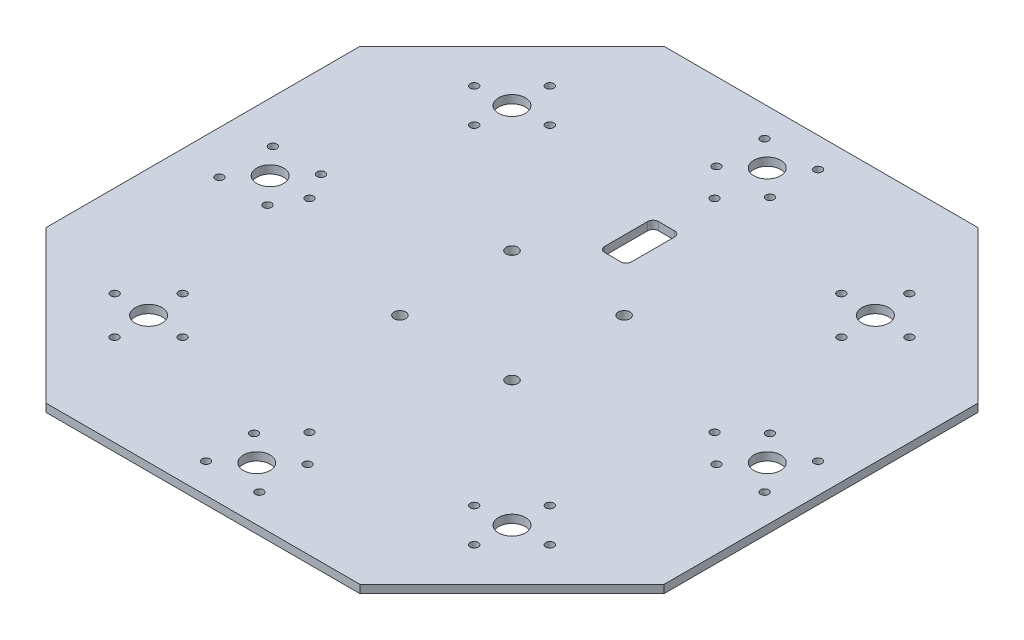
SolidWorks part; units mm, degrees
ref_plane "Front Plane" through (0, 0, 0) normal (0, 0, 1) x (1, 0, 0)
ref_plane "Top Plane" through (0, 0, 0) normal (0, 1, 0) x (1, 0, 0)
ref_plane "Right Plane" through (0, 0, 0) normal (1, 0, 0) x (0, 0, -1)
sketch "Sketch1" plane through (0, 0, 0) normal (0, 1, 0) x (1, 0, 0)
  line L1 (0, 0) -> (230, 0)
  line L2 (0, 0) -> (0, 230)
  line L3 (0, 230) -> (230, 230)
  line L4 (230, 0) -> (230, 230)
  dimension "D1" = 230
  dimension "D2" = 230
extrude "Boss-Extrude1" add sketch "Sketch1" along normal blind 3
fillet "Chamfer2" radius 56.5685 1 edges at (0, 1.5, 0) type face fillet profile chamfer first side face at (115, 1.5, 0) second side face at (0, 1.5, -115)
fillet "Chamfer3" radius 56.5685 1 edges at (0, 1.5, -230) type face fillet profile chamfer first side face at (0, 1.5, -143.2843) second side face at (115, 1.5, -230)
fillet "Chamfer4" radius 56.5685 1 edges at (230, 1.5, -230) type face fillet profile chamfer first side face at (143.2842, 1.5, -230) second side face at (230, 1.5, -115)
fillet "Chamfer5" radius 56.5685 1 edges at (230, 1.5, 0) type face fillet profile chamfer first side face at (230, 1.5, -86.7158) second side face at (143.2843, 1.5, 0)
hole_wizard "11/64 (0.17188) Diameter Hole1" positions "Sketch4" profile "Sketch3" hole size "11/64" standard "ANSI Inch" end condition up to next
sketch "Sketch4" plane through (0, 3, 0) normal (0, 1, 0) x (1, 0, 0)
  point P0 (94.1403, 135.8597)
  point P3 (135.8597, 135.8597)
  point P6 (135.8597, 94.1403)
  point P9 (94.1403, 94.1403)
sketch "Sketch3" plane through (94.1403, 3, -135.8597) normal (1, 0, 0) x (0, 0, 1)
  line L0 (0, 0) -> (0, 3)
  line L1 (0, 3) -> (2.1829, 3)
  line L2 (2.1829, 3) -> (2.1829, 0)
  line L5 (2.1829, 0) -> (0, 0)
  line L11 (0, -6.35) -> (0, 107.95) construction
  dimension "Thru Hole Dia." = 4.3658
  dimension "Thru Hole Depth" = 3
sketch "Sketch11" plane through (0, 3, 0) normal (0, 1, 0) x (1, 0, 0)
  line L0 (230, 115) -> (0, 115) construction
  line L1 (230, 56.5685) -> (230, 173.4315) construction
  line L2 (0, 173.4315) -> (0, 56.5685) construction
  line L4 (115, 115) -> (115, 152.5) construction
  line L5 (115, 152.5) -> (120, 152.5)
  line L6 (115, 152.5) -> (110, 152.5)
  line L7 (120, 152.5) -> (120, 172.5)
  line L8 (120, 172.5) -> (110, 172.5)
  line L9 (110, 152.5) -> (110, 172.5)
extrude "Cut-Extrude3" cut sketch "Sketch11" against normal through all
fillet "Fillet9" radius 2 1 edges at (120, 1.5, -172.5) type face fillet first side face at (120, 1.5, -162.5) second side face at (115, 1.5, -172.5)
fillet "Fillet10" radius 2 1 edges at (110, 1.5, -172.5) type face fillet first side face at (114, 1.5, -172.5) second side face at (110, 1.5, -162.5)
fillet "Fillet11" radius 2 1 edges at (120, 1.5, -152.5) type face fillet first side face at (120, 1.5, -161.5) second side face at (115, 1.5, -152.5)
fillet "Fillet12" radius 2 1 edges at (110, 1.5, -152.5) type face fillet first side face at (114, 1.5, -152.5) second side face at (110, 1.5, -161.5)
hole_wizard "Ø10.0mm Dowel Hole1" positions "Sketch12" profile "Sketch13" hole size "Ø10.0" standard "ANSI Metric" end condition up to next
sketch "Sketch12" plane through (0, 3, 0) normal (0, 1, 0) x (1, 0, 0)
  point P0 (210, 115)
  point P3 (182.6239, 182.6239)
  point P6 (182.6239, 47.3761)
  point P9 (115, 20)
  point P12 (47.3761, 47.3761)
  point P15 (25, 115)
  point P18 (47.3761, 182.6239)
  point P21 (115, 210)
sketch "Sketch13" plane through (210, 3, -115) normal (1, 0, 0) x (0, 0, 1)
  line L0 (0, 0) -> (0, 3)
  line L1 (0, 3) -> (5, 3)
  line L2 (5, 3) -> (5, 0)
  line L5 (5, 0) -> (0, 0)
  line L11 (0, -6.35) -> (0, 107.95) construction
  dimension "Thru Hole Dia." = 10
  dimension "Thru Hole Depth" = 3
hole_wizard "Ø3.0mm Dowel Hole1" positions "Sketch16" profile "Sketch15" hole size "Ø3.0" standard "ANSI Metric" end condition up to next
sketch "Sketch16" plane through (0, 0, 0) normal (0, -1, 0) x (-1, 0, 0)
  point P0 (-201.05, 124.95)
  point P3 (-201.05, 105.05)
  point P6 (-218.95, 124.95)
  point P9 (-218.95, 105.05)
  point P12 (-183.331, 60.7405)
  point P15 (-169.2595, 46.669)
  point P18 (-181.9168, 34.0118)
  point P21 (-195.9882, 48.0832)
  point P24 (-183.331, 169.2595)
  point P27 (-169.2595, 183.331)
  point P30 (-181.9168, 195.9882)
  point P33 (-195.9882, 181.9168)
  point P36 (-124.95, 201.05)
  point P39 (-124.95, 218.95)
  point P42 (-105.05, 218.95)
  point P45 (-105.05, 201.05)
  point P48 (-60.7405, 183.331)
  point P51 (-34.0118, 181.9168)
  point P54 (-46.669, 169.2595)
  point P57 (-48.0832, 195.9882)
  point P60 (-16.05, 124.95)
  point P63 (-33.95, 105.05)
  point P66 (-33.95, 124.95)
  point P69 (-16.05, 105.05)
  point P72 (-60.7405, 46.669)
  point P75 (-48.0832, 34.0118)
  point P78 (-46.669, 60.7405)
  point P81 (-34.0118, 48.0832)
  point P84 (-105.05, 28.95)
  point P87 (-105.05, 11.05)
  point P90 (-124.95, 28.95)
  point P93 (-124.95, 11.05)
sketch "Sketch15" plane through (201.05, 0, -124.95) normal (1, 0, 0) x (0, 0, -1)
  line L0 (0, 0) -> (0, 3)
  line L1 (0, 3) -> (1.5, 3)
  line L2 (1.5, 3) -> (1.5, 0)
  line L5 (1.5, 0) -> (0, 0)
  line L11 (0, -6.35) -> (0, 107.95) construction
  dimension "Thru Hole Dia." = 3
  dimension "Thru Hole Depth" = 3
hole_wizard "Ø3.0mm Dowel Hole2" positions "Sketch17" profile "Sketch18" hole size "Ø3.0" standard "ANSI Metric" end condition up to next
sketch "Sketch17" plane through (0, 3, 0) normal (0, 1, 0) x (1, 0, 0)
  point P0 (115, 190.375)
  point P3 (39.625, 115)
  point P6 (115, 39.625)
  point P9 (190.375, 115)
sketch "Sketch18" plane through (115, 3, -190.375) normal (1, 0, 0) x (0, 0, 1)
  line L0 (0, 0) -> (0, 3)
  line L1 (0, 3) -> (1.5, 3)
  line L2 (1.5, 3) -> (1.5, 0)
  line L5 (1.5, 0) -> (0, 0)
  line L11 (0, -6.35) -> (0, 107.95) construction
  dimension "Thru Hole Dia." = 3
  dimension "Thru Hole Depth" = 3
